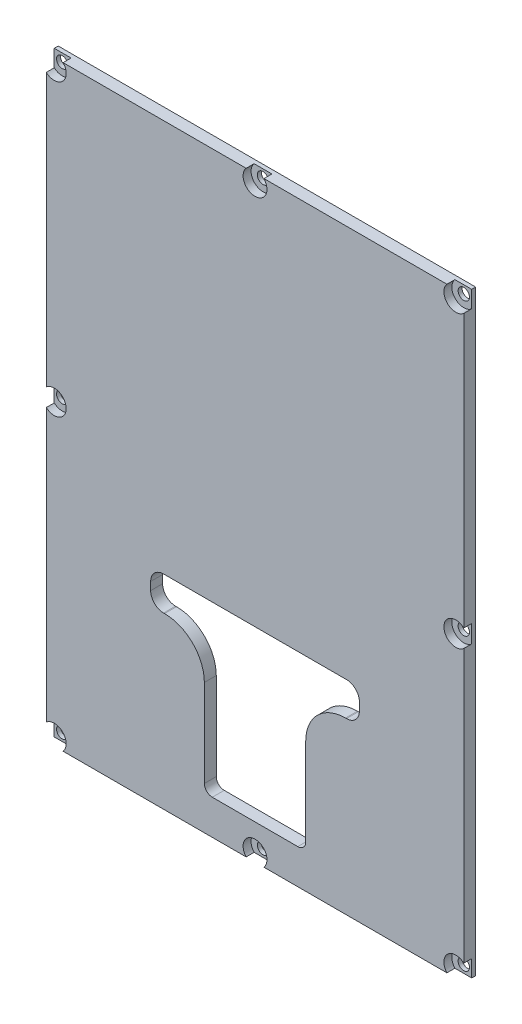
SolidWorks part; units mm, degrees
ref_plane "Спереди" through (0, 0, 0) normal (0, 0, 1) x (1, 0, 0)
ref_plane "Сверху" through (0, 0, 0) normal (0, 1, 0) x (1, 0, 0)
ref_plane "Справа" through (0, 0, 0) normal (1, 0, 0) x (0, 0, -1)
sketch "Эскиз1" plane through (0, 0, 0) normal (0, 0, 1) x (1, 0, 0)
  line L1 (-52.5, -75) -> (52.5, -75)
  line L2 (-52.5, -75) -> (-52.5, 75)
  line L3 (-52.5, 75) -> (52.5, 75)
  line L4 (52.5, -75) -> (52.5, 75)
  line L5 (-52.5, -75) -> (52.5, 75) construction
  line L6 (-52.5, 75) -> (52.5, -75) construction
  point P0 (0, 0)
  dimension "D1" = 105
  dimension "D2" = 150
extrude "Бобышка-Вытянуть1" add sketch "Эскиз1" along normal blind 3
sketch "Эскиз2" plane through (0, 0, 0) normal (0, 0, -1) x (-1, 0, 0)
  line L0 (-26.25, -27) -> (-26.25, -29)
  line L1 (-23, -32.25) -> (-22.75, -32.25)
  line L2 (-12.75, -42.25) -> (-12.75, -64.25)
  line L3 (-10.75, -66.25) -> (10.75, -66.25)
  line L4 (12.75, -64.25) -> (12.75, -42.25)
  line L5 (22.75, -32.25) -> (23, -32.25)
  line L6 (26.25, -29) -> (26.25, -27)
  line L7 (23, -23.75) -> (-23, -23.75)
  line L8 (-52.5, -75) -> (-52.5, 75) construction
  line L9 (52.5, 75) -> (52.5, -75) construction
  line L10 (52.5, -75) -> (-52.5, -75) construction
  arc A0 (22.75, -32.25) -> (12.75, -42.25) centre (22.75, -42.25) ccw
  arc A1 (-12.75, -42.25) -> (-22.75, -32.25) centre (-22.75, -42.25) ccw
  arc A2 (23, -32.25) -> (26.25, -29) centre (23, -29) ccw
  arc A3 (26.25, -27) -> (23, -23.75) centre (23, -27) ccw
  arc A4 (-23, -32.25) -> (-26.25, -29) centre (-23, -29) cw
  arc A5 (-23, -23.75) -> (-26.25, -27) centre (-23, -27) ccw
  arc A6 (12.75, -64.25) -> (10.75, -66.25) centre (10.75, -64.25) cw
  arc A7 (-10.75, -66.25) -> (-12.75, -64.25) centre (-10.75, -64.25) cw
  point P16 (12.75, -32.25)
  point P21 (26.25, -32.25)
  point P24 (26.25, -23.75)
  point P31 (12.75, -66.25)
  point P34 (-12.75, -66.25)
  dimension "D7" = 10
  dimension "D8" = 3.25
  dimension "D9" = 2
  dimension "D1" = 26.25
  dimension "D2" = 26.25
  dimension "D3" = 51.25
  dimension "D4" = 8.5
  dimension "D5" = 25.5
  dimension "D6" = 34
extrude "Вырез-Вытянуть1" cut sketch "Эскиз2" against normal blind 10
sketch "Эскиз3" plane through (0, 0, 3) normal (0, 0, 1) x (1, 0, 0)
  line L0 (-50.5, -940.9285) -> (-50.5, 49059.0715) construction
  line L1 (50.5, -944.6511) -> (50.5, 49055.3489) construction
  line L2 (-1032.3277, 73) -> (48967.6723, 73) construction
  line L3 (-1028.801, -73) -> (48971.199, -73) construction
  line L4 (-52.5, -75) -> (52.5, -75) construction
  line L6 (-52.5, 75) -> (-52.5, -75) construction
  line L7 (52.5, -75) -> (52.5, 75) construction
  line L8 (52.5, 75) -> (-52.5, 75) construction
  line L9 (0, -925) -> (0, 49075) construction
  line L10 (-1052.5, 0) -> (48947.5, 0) construction
  circle A0 centre (-50.5, 73) radius 3
  circle A1 centre (0, 73) radius 3
  circle A2 centre (50.5, 73) radius 3
  circle A3 centre (50.5, 0) radius 3
  circle A4 centre (50.5, -73) radius 3
  circle A5 centre (0, -73) radius 3
  circle A6 centre (-50.5, -73) radius 3
  circle A7 centre (-50.5, 0) radius 3
  point P19 (0, 75)
  point P22 (-52.5, 0)
  point P38 (0, 0)
  dimension "D5" = 6
  dimension "D1" = 2
  dimension "D2" = 2
  dimension "D3" = 2
  dimension "D4" = 2
extrude "Вырез-Вытянуть2" cut sketch "Эскиз3" against normal blind 2
sketch "Эскиз4" plane through (0, 0, 1) normal (0, 0, 1) x (1, 0, 0)
  circle A0 centre (-50.5, 73) radius 1.425
  circle A1 centre (0, 73) radius 1.425
  circle A2 centre (50.5, 73) radius 1.425
  circle A3 centre (50.5, 0) radius 1.425
  circle A4 centre (50.5, -73) radius 1.425
  circle A5 centre (0, -73) radius 1.425
  circle A6 centre (-50.5, -73) radius 1.425
  circle A7 centre (-50.5, 0) radius 1.425
  dimension "D1" = 2.85
extrude "Вырез-Вытянуть3" cut sketch "Эскиз4" against normal blind 2
